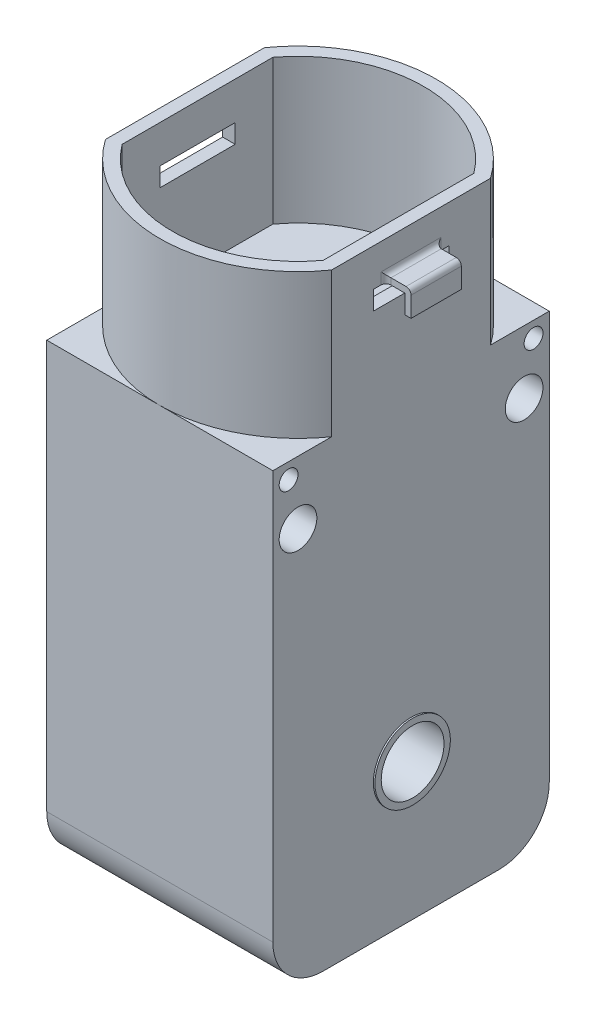
SolidWorks part; units mm, degrees
ref_plane "Front Plane" through (0, 0, 0) normal (0, 0, 1) x (1, 0, 0)
ref_plane "Top Plane" through (0, 0, 0) normal (0, 1, 0) x (1, 0, 0)
ref_plane "Right Plane" through (0, 0, 0) normal (1, 0, 0) x (0, 0, -1)
sketch "Sketch1" plane through (0, 0, 0) normal (0, 1, 0) x (1, 0, 0)
  line L1 (-9, 11) -> (9, 11)
  line L2 (-9, 11) -> (-9, -11)
  line L3 (-9, -11) -> (9, -11)
  line L4 (9, 11) -> (9, -11)
  line L5 (-9, 11) -> (9, -11) construction
  line L6 (-9, -11) -> (9, 11) construction
  point P0 (0, 0)
  dimension "D1" = 18
  dimension "D2" = 22
extrude "Boss-Extrude1" add sketch "Sketch1" along normal blind 36.5
fillet "Fillet1" radius 4 2 edges at (0, 0, -11) (0, 0, 11)
sketch "Sketch2" plane through (0, 36.5, 0) normal (0, 1, 0) x (1, 0, 0)
  line L0 (-9, 11) -> (-9, -11) construction
  line L1 (-9, 6.3246) -> (-9, -6.3246)
  line L2 (9, -11) -> (9, 11) construction
  line L3 (9, -6.3246) -> (9, 6.3246)
  line L4 (-8, 6) -> (-8, -6)
  line L5 (8, -6) -> (8, 6)
  arc A0 (-9, -6.3246) -> (9, -6.3246) centre (0, 0) ccw
  arc A1 (9, 6.3246) -> (-9, 6.3246) centre (0, 0) ccw
  arc A2 (8, 6) -> (-8, 6) centre (0, 0) ccw
  arc A3 (-8, -6) -> (8, -6) centre (0, 0) ccw
  dimension "D1" = 1
extrude "Boss-Extrude2" add sketch "Sketch2" along normal blind 11.5
sketch "Sketch3" plane through (0, 0, 0) normal (0, 0, 1) x (1, 0, 0)
  line L0 (-9, 45) -> (-10.5, 45)
  line L1 (-9, 48) -> (-9, 36.5) construction
  line L2 (-10.5, 45) -> (-10.5, 43.5)
  line L3 (-9, 45.5) -> (-11, 45.5)
  line L4 (-11, 45.5) -> (-11, 43.5)
  line L5 (-11, 43.5) -> (-10.5, 43.5)
  line L6 (-9, 45) -> (-9, 45.5)
  dimension "D1" = 3
  dimension "D2" = 1.5
  dimension "D3" = 1.5
  dimension "D4" = 0.5
extrude "Boss-Extrude3" add sketch "Sketch3" along normal mid plane 4
sketch "Sketch4" plane through (-9, 0, 0) normal (-1, 0, 0) x (0, 0, 1)
  line L1 (-3, 45) -> (3, 45)
  line L2 (-3, 45) -> (-3, 43.5)
  line L3 (-3, 43.5) -> (3, 43.5)
  line L4 (3, 45) -> (3, 43.5)
  point P6 (0, 45)
  dimension "D1" = 6
  dimension "D2" = 1.5
extrude "Cut-Extrude1" cut sketch "Sketch4" against normal blind 4
fillet "Fillet2" radius 0.4 3 edges at (-9, 45.25, -2) (-9, 45.5, 0) (-9, 45.25, 2)
fillet "Fillet3" radius 0.4 1 edges at (-11, 45.5, 0)
mirror "Mirror1" about plane through (0, 0, 0) normal (1, 0, 0) of "Cut-Extrude1", "Boss-Extrude3"
fillet "Fillet4" radius 0.4 4 edges at (11, 45.5, 0) (9, 45.25, -2) (9, 45.5, 0) (9, 45.25, 2)
sketch "Sketch5" plane through (-9, 0, 0) normal (-1, 0, 0) x (0, 0, 1)
  line L0 (6.3246, 36.5) -> (11, 36.5) construction
  line L2 (11, 36.5) -> (11, 4) construction
  circle A0 centre (9, 31.5) radius 1.5
  circle A1 centre (6, 34) radius 2
  circle A2 centre (6, 34) radius 2.45
  dimension "D1" = 3
  dimension "D4" = 4
  dimension "D2" = 5
  dimension "D3" = 2
  dimension "D5" = 2.5
  dimension "D6" = 5
  dimension "D7" = 0.45
extrude "Cut-Extrude2" cut sketch "Sketch5" against normal through all contours A2 A0 | A0 A2 region at (-9, 31.4977, 9.0028) region at (-9, 32.4452, 7.8657)
extrude "Cut-Extrude3" cut sketch "Sketch5<3>" against normal blind 1 contours A0 A2 A1 | A1 | A0 A2 region at (-9, 32.4452, 7.8657) region at (-9, 32.5046, 7.7944) region at (-9, 34, 6)
sketch "Sketch5<3>" plane through (-9, 0, 0) normal (-1, 0, 0) x (0, 0, 1) same geometry as "Sketch5"
sketch "Sketch6" plane through (-8, 0, 0) normal (-1, 0, 0) x (0, 0, 1)
  circle A0 centre (6, 34) radius 0.75
  dimension "D1" = 1.5
extrude "Cut-Extrude4" cut sketch "Sketch6" against normal blind 9
mirror "Mirror4" about plane through (0, 0, 0) normal (0, 0, 1) of "Cut-Extrude2", "Cut-Extrude4", "Cut-Extrude3"
sketch "Sketch7" plane through (9, 0, 0) normal (1, 0, 0) x (0, 0, -1)
  line L0 (-11, 36.5) -> (-11, 4) construction
  line L1 (-6.3246, 36.5) -> (-11, 36.5) construction
  circle A0 centre (-9.75, 35.25) radius 0.75
  dimension "D1" = 1.5
  dimension "D2" = 1.25
  dimension "D3" = 1.25
extrude "Cut-Extrude5" cut sketch "Sketch7" against normal up to surface (8 mm away) up to face at (1, 34, 6.75)
mirror "Mirror5" about plane through (0, 0, 0) normal (0, 0, 1) of "Cut-Extrude5"
sketch "Sketch8" plane through (-9, 0, 0) normal (-1, 0, 0) x (0, 0, 1)
  line L0 (-7, 0) -> (7, 0) construction
  circle A0 centre (0, 11) radius 2.5
  circle A1 centre (0, 22) radius 1.5
  circle A2 centre (0, 11) radius 3
  dimension "D3" = 5
  dimension "D4" = 3
  dimension "D1" = 11
  dimension "D2" = 22
  dimension "D5" = 0.5
extrude "Cut-Extrude6" cut sketch "Sketch8" against normal through all contours A0 region at (-9, 11, 0)
extrude "Boss-Extrude4" add sketch "Sketch8<3>" along normal blind 0.125 contours A2 A0 region at (-9, 11, -2.9151)
sketch "Sketch8<3>" plane through (-9, 0, 0) normal (-1, 0, 0) x (0, 0, 1) same geometry as "Sketch8"
ref_plane "Plane1" through (0, 22, 0) normal (0, -1, 0) x (-1, 0, 0)
sketch "Sketch9" plane through (0, 22, 0) normal (0, -1, 0) x (-1, 0, 0)
  line L0 (9, 1.5) -> (9, -1.5)
  arc A0 (9, -1.5) -> (9, 1.5) centre (9, 0) ccw
  dimension "D1" = 3
revolve "Revolve1" add sketch "Sketch9" angle 360 about L0
mirror "Mirror6" about plane through (0, 0, 0) normal (1, 0, 0) of "Boss-Extrude4"
sketch "Sketch11" plane through (0, 0, 0) normal (1, 0, 0) x (0, 0, -1)
  line L0 (-7, 0) -> (7, 0) construction
  line L1 (-2.5, -2.8108) -> (-2.5, 0)
  line L2 (-2.5, 0) -> (2.5, 0)
  line L3 (2.5, 0) -> (2.5, -2.8108)
  line L4 (-2.5, -2.8108) -> (-2.5, -5)
  line L5 (-2.5, -5) -> (2.5, -5)
  line L6 (2.5, -5) -> (2.5, -2.8108)
  circle A0 centre (0, -2.5) radius 1.5
  point P4 (0, -2.8108)
  point P8 (2.5, -2.5)
  dimension "D1" = 3
  dimension "D2" = 2.5
  dimension "D3" = 2.5
extrude "Boss-Extrude5" add sketch "Sketch11" along normal mid plane 2.5
